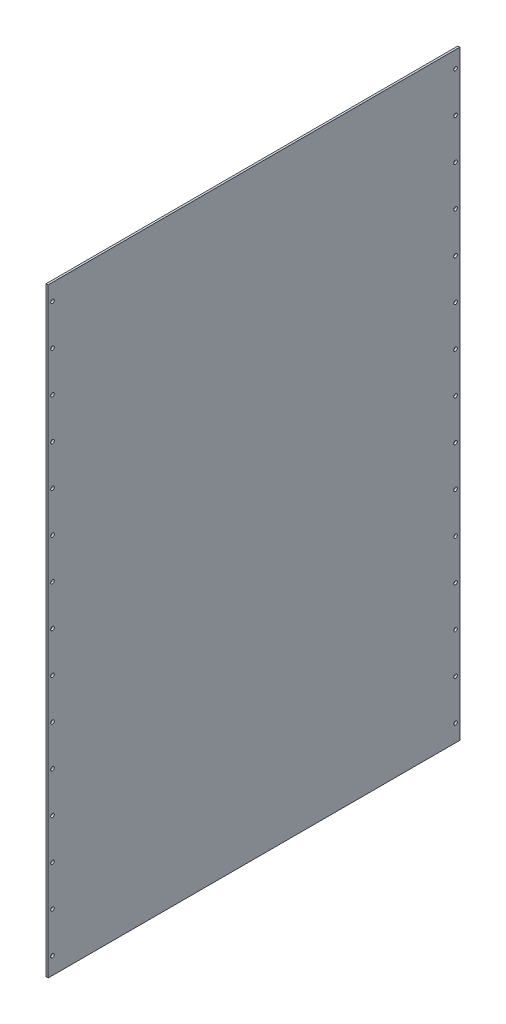
SolidWorks part; units mm, degrees
ref_plane "Front" through (0, 0, 0) normal (0, 0, 1) x (1, 0, 0)
ref_plane "Top" through (0, 0, 0) normal (0, 1, 0) x (1, 0, 0)
ref_plane "Right" through (0, 0, 0) normal (1, 0, 0) x (0, 0, -1)
sketch "Sketch1" plane through (0, 0, 0) normal (1, 0, 0) x (0, 0, -1)
  line L1 (0, 0) -> (609.6, 0)
  line L2 (0, 0) -> (0, 889)
  line L3 (0, 889) -> (609.6, 889)
  line L4 (609.6, 0) -> (609.6, 889)
  dimension "D1" = 889
  dimension "D2" = 609.6
extrude "Boss-Extrude1" add sketch "Sketch1" along normal blind 3
sketch "Sketch2" plane through (3, 0, 0) normal (1, 0, 0) x (0, 0, -1)
  line L0 (304.8, 0) -> (304.8, 25.4) construction
  line L1 (0, 0) -> (609.6, 0) construction
  line L2 (6.35, 25.4) -> (603.25, 25.4) construction
  line L3 (603.25, 25.4) -> (609.6, 25.4) construction
  line L4 (609.6, 0) -> (609.6, 889) construction
  line L5 (6.35, 25.4) -> (0, 25.4) construction
  line L6 (0, 889) -> (0, 0) construction
  line L7 (6.35, 25.4) -> (603.25, 25.4) construction
  circle A0 centre (6.35, 25.4) radius 2.667
  circle A1 centre (603.25, 25.4) radius 2.667
  circle A2 centre (603.25, 85.344) radius 2.667
  circle A3 centre (603.25, 145.288) radius 2.667
  circle A4 centre (603.25, 205.232) radius 2.667
  circle A5 centre (603.25, 265.176) radius 2.667
  circle A6 centre (603.25, 325.12) radius 2.667
  circle A7 centre (603.25, 385.064) radius 2.667
  circle A8 centre (603.25, 445.008) radius 2.667
  circle A9 centre (603.25, 504.952) radius 2.667
  circle A10 centre (603.25, 564.896) radius 2.667
  circle A11 centre (603.25, 624.84) radius 2.667
  circle A12 centre (603.25, 684.784) radius 2.667
  circle A13 centre (603.25, 744.728) radius 2.667
  circle A14 centre (603.25, 804.672) radius 2.667
  circle A15 centre (603.25, 864.616) radius 2.667
  circle A16 centre (6.35, 85.344) radius 2.667
  circle A17 centre (6.35, 145.288) radius 2.667
  circle A18 centre (6.35, 205.232) radius 2.667
  circle A19 centre (6.35, 265.176) radius 2.667
  circle A20 centre (6.35, 325.12) radius 2.667
  circle A21 centre (6.35, 385.064) radius 2.667
  circle A22 centre (6.35, 445.008) radius 2.667
  circle A23 centre (6.35, 504.952) radius 2.667
  circle A24 centre (6.35, 564.896) radius 2.667
  circle A25 centre (6.35, 624.84) radius 2.667
  circle A26 centre (6.35, 684.784) radius 2.667
  circle A27 centre (6.35, 744.728) radius 2.667
  circle A28 centre (6.35, 804.672) radius 2.667
  circle A29 centre (6.35, 864.616) radius 2.667
  dimension "D3" = 5.334
  dimension "D1" = 25.4
  dimension "=D6" = 596.9
  dimension "D6" = 596.9
  dimension "D4" = 2
  dimension "D5" = 15
extrude "Cut-Extrude1" cut sketch "Sketch2" against normal up to next (3 mm away)
